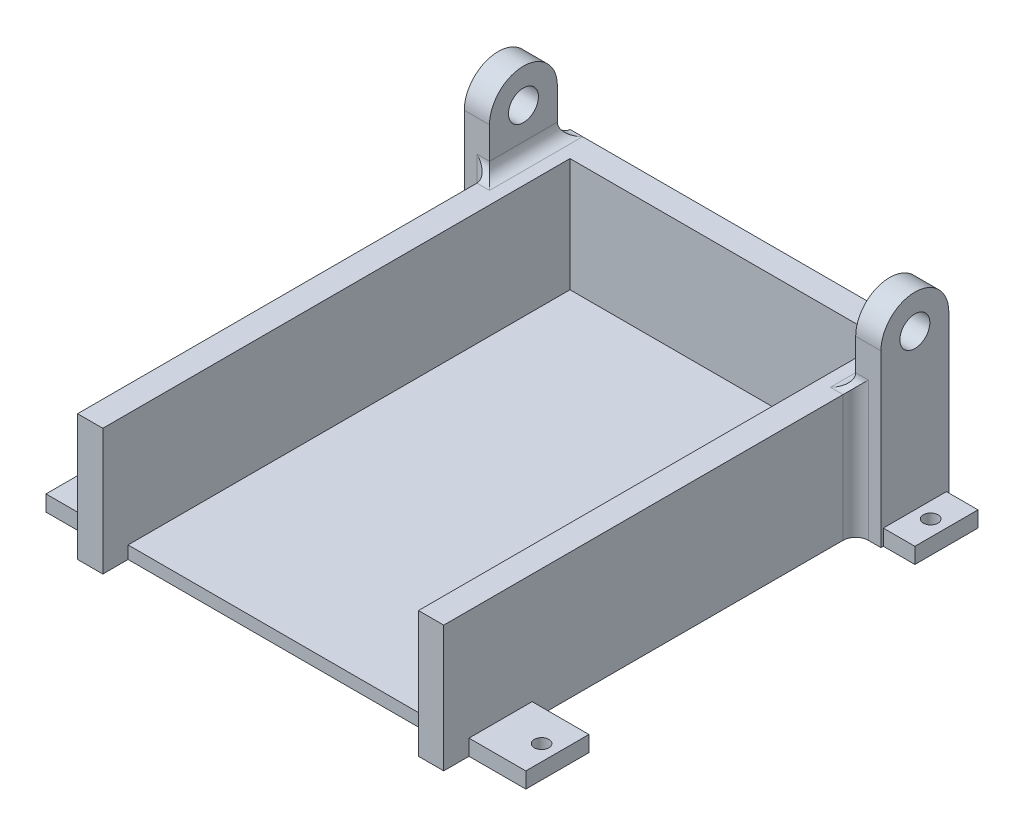
SolidWorks part; units mm, degrees
ref_plane "Front Plane" through (0, 0, 0) normal (0, 0, 1) x (1, 0, 0)
ref_plane "Top Plane" through (0, 0, 0) normal (0, 1, 0) x (1, 0, 0)
ref_plane "Right Plane" through (0, 0, 0) normal (1, 0, 0) x (0, 0, -1)
sketch "Sketch3" plane through (0, 0, 0) normal (0, 1, 0) x (1, 0, 0)
  line L0 (-36.83, 49.53) -> (36.83, 49.53)
  line L1 (-31.75, -44.45) -> (31.75, -44.45)
  line L2 (-31.75, -44.45) -> (-31.75, 44.45)
  line L3 (-31.75, 44.45) -> (31.75, 44.45)
  line L4 (31.75, -44.45) -> (31.75, 44.45)
  line L5 (-31.75, -44.45) -> (31.75, 44.45) construction
  line L6 (-31.75, 44.45) -> (31.75, -44.45) construction
  line L7 (36.83, -49.53) -> (36.83, 49.53)
  line L8 (-36.83, -49.53) -> (36.83, -49.53)
  line L9 (-36.83, -49.53) -> (-36.83, 49.53)
  point P0 (0, 0)
  dimension "D1" = 88.9
  dimension "D2" = 63.5
  dimension "D3" = 5.08
extrude "Boss-Extrude1" add sketch "Sketch3" along normal blind 2.54 contours L1 L4 L3 L2 region at (0, 0, 0)
sketch "Sketch4" plane through (0, 0, 0) normal (0, 1, 0) x (1, 0, 0)
  line L0 (-31.75, -44.45) -> (-31.75, 44.45) construction
  line L1 (-31.75, 44.45) -> (31.75, 44.45) construction
  line L2 (31.75, -44.45) -> (31.75, 44.45) construction
  line L3 (36.83, -49.53) -> (36.83, 49.53) construction
  line L4 (-36.83, 49.53) -> (36.83, 49.53) construction
  line L5 (-36.83, -49.53) -> (-36.83, 49.53) construction
  line L6 (-31.75, -44.45) -> (-31.75, 44.45)
  line L7 (-31.75, 44.45) -> (31.75, 44.45)
  line L8 (31.75, -44.45) -> (31.75, 44.45)
  line L9 (36.83, -49.53) -> (36.83, 49.53)
  line L10 (-36.83, 49.53) -> (36.83, 49.53)
  line L11 (-36.83, -49.53) -> (-36.83, 49.53)
  line L12 (-31.75, -44.45) -> (-31.75, -49.53)
  line L13 (-36.83, -49.53) -> (36.83, -49.53) construction
  line L14 (-31.75, -49.53) -> (-36.83, -49.53)
  line L15 (31.75, -44.45) -> (31.75, -49.53)
  line L16 (31.75, -49.53) -> (36.83, -49.53)
extrude "Boss-Extrude2" add sketch "Sketch4" along normal blind 25.4
sketch "Sketch5" plane through (-36.83, 0, 0) normal (-1, 0, 0) x (0, 0, 1)
  line L0 (-46.99, 34.29) -> (-46.99, 0)
  line L1 (-49.53, 0) -> (49.53, 0) construction
  line L2 (-46.99, 0) -> (-33.3375, 0)
  line L3 (-33.3375, 0) -> (-33.3375, 34.29)
  line L4 (-49.53, 25.4) -> (-49.53, 0) construction
  line L5 (44.45, 2.54) -> (-44.45, 2.54) construction
  line L6 (44.45, 2.54) -> (-44.45, 2.54) construction
  line L7 (44.45, 2.54) -> (44.45, 21.59) construction
  line L8 (44.45, 21.59) -> (-44.45, 21.59) construction
  line L9 (-44.45, 2.54) -> (-44.45, 21.59) construction
  line L10 (44.45, 2.54) -> (-44.45, 21.59) construction
  line L11 (44.45, 21.59) -> (-44.45, 2.54) construction
  line L12 (44.45, 2.54) -> (-44.45, 2.54) construction
  line L13 (-44.45, 25.4) -> (-44.45, 2.54) construction
  line L14 (29.6862, 34.29) -> (-40.1638, 34.29) construction
  line L15 (-40.1638, 34.29) -> (27.0383, 53.34) construction
  line L16 (-40.1638, 34.29) -> (28.8682, 44.9491) construction
  circle A0 centre (-40.1638, 34.29) radius 3.0163
  arc A1 (-46.99, 34.29) -> (-33.3375, 34.29) centre (-40.1638, 34.29) cw
  circle A2 centre (27.0383, 53.34) radius 31.75 construction
  circle A3 centre (29.6862, 34.29) radius 31.75 construction
  circle A4 centre (28.8682, 44.9491) radius 31.75 construction
  point P12 (0, 12.065)
  dimension "D1" = 6.0325
  dimension "D3" = 3.81
  dimension "D6" = 63.5
  dimension "D2" = 2.54
  dimension "D4" = 88.9
  dimension "D5" = 19.05
  dimension "D7" = 12.7
  dimension "D8" = 69.85
extrude "Boss-Extrude3" add sketch "Sketch5" along normal blind 5.08
mirror "Mirror1" about plane through (0, 0, 0) normal (1, 0, 0) of "Boss-Extrude3"
fillet "Fillet1" radius 2.54 4 edges at (36.83, 12.7, -46.99) (36.83, 12.7, -33.3375) (-36.83, 12.7, -46.99) (-36.83, 12.7, -33.3375)
fillet "Fillet2" radius 2.54 6 edges at (38.1, 25.4, -33.3375) (36.83, 25.4, -40.1638) (38.1, 25.4, -46.99) (-38.1, 25.4, -46.99) (-36.83, 25.4, -40.1638) (-38.1, 25.4, -33.3375)
sketch "Sketch6" plane through (-41.91, 0, 0) normal (-1, 0, 0) x (0, 0, 1)
  line L0 (-46.99, 0) -> (-33.3375, 0) construction
  line L1 (-46.5137, 0) -> (-33.8137, 0)
  line L2 (-46.5137, 0) -> (-46.5137, 3.175)
  line L3 (-46.5137, 3.175) -> (-33.8137, 3.175)
  line L4 (-33.8137, 0) -> (-33.8137, 3.175)
  line L5 (-46.99, 34.29) -> (-46.99, 0) construction
  dimension "D1" = 12.7
  dimension "D2" = 3.175
  dimension "D3" = 0.4762
extrude "Boss-Extrude4" add sketch "Sketch6" along normal blind 6.35
sketch "Sketch7" plane through (0, 3.175, 0) normal (0, 1, 0) x (1, 0, 0)
  line L0 (-45.085, 40.1637) -> (-48.26, 40.1637) construction
  line L1 (-48.26, 33.8137) -> (-48.26, 46.5137) construction
  line L2 (-45.085, 40.1637) -> (-45.085, 46.5137) construction
  line L3 (-48.26, 46.5137) -> (-41.91, 46.5137) construction
  circle A0 centre (-45.085, 40.1637) radius 1.4732
  dimension "D1" = 2.9464
extrude "Cut-Extrude1" cut sketch "Sketch7" against normal up to next
sketch "Sketch8" plane through (-36.83, 0, 0) normal (-1, 0, 0) x (0, 0, 1)
  line L1 (49.53, 25.4) -> (49.53, 0) construction
  line L2 (-30.7975, 0) -> (49.53, 0) construction
  line L3 (44.45, 3.175) -> (31.75, 3.175)
  line L4 (44.45, 3.175) -> (44.45, 0)
  line L5 (44.45, 0) -> (31.75, 0)
  line L6 (31.75, 3.175) -> (31.75, 0)
  dimension "D1" = 3.175
  dimension "D2" = 12.7
  dimension "D3" = 5.08
extrude "Boss-Extrude5" add sketch "Sketch8" along normal blind 11.43
sketch "Sketch9" plane through (0, 3.175, 0) normal (0, 1, 0) x (1, 0, 0)
  line L0 (-36.83, 30.7975) -> (-36.83, -49.53) construction
  line L1 (-48.26, -31.75) -> (-36.83, -31.75) construction
  circle A0 centre (-45.085, -38.1) radius 1.4732
  dimension "D1" = 8.255
  dimension "D2" = 2.9464
  dimension "D3" = 6.35
extrude "Cut-Extrude2" cut sketch "Sketch9" against normal up to next
mirror "Mirror2" about plane through (0, 0, 0) normal (1, 0, 0) of "Cut-Extrude2", "Cut-Extrude1", "Boss-Extrude5", "Boss-Extrude4"
